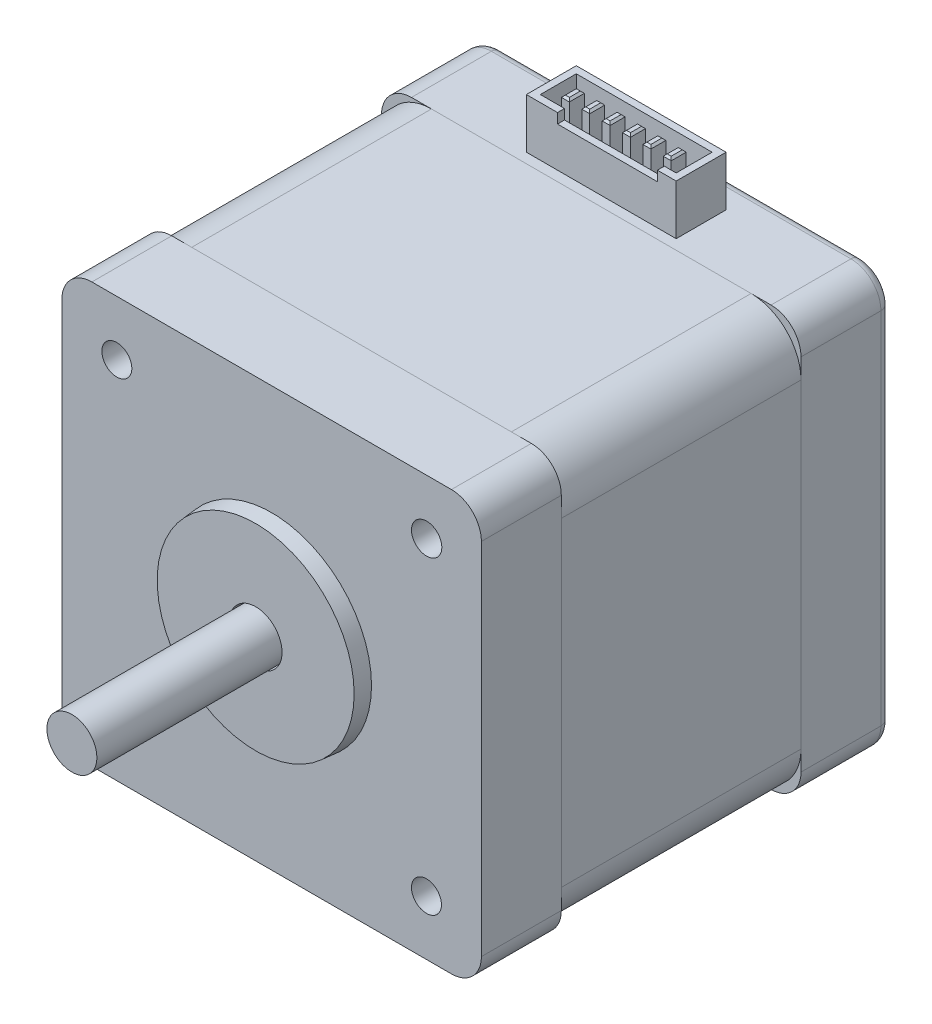
SolidWorks part; units mm, degrees
material "氧化铝"
ref_plane "前视基准面" through (0, 0, 0) normal (0, 0, 1) x (1, 0, 0)
ref_plane "上视基准面" through (0, 0, 0) normal (0, 1, 0) x (1, 0, 0)
ref_plane "右视基准面" through (0, 0, 0) normal (1, 0, 0) x (0, 0, -1)
sketch "草图1" plane through (0, 0, 0) normal (0, 0, 1) x (1, 0, 0)
  line L0 (0, 21) -> (0, -21) construction
  line L1 (-18, 21) -> (18, 21)
  line L2 (-21, 18) -> (-21, -18)
  line L3 (-18, -21) -> (18, -21)
  line L4 (21, 18) -> (21, -18)
  line L5 (-21, 21) -> (21, -21) construction
  line L6 (-21, -21) -> (21, 21) construction
  line L7 (-15.5, 15.5) -> (15.5, 15.5) construction
  line L8 (-15.5, 15.5) -> (-15.5, -15.5) construction
  line L9 (-15.5, -15.5) -> (15.5, -15.5) construction
  line L10 (15.5, 15.5) -> (15.5, -15.5) construction
  line L11 (-15.5, 15.5) -> (15.5, -15.5) construction
  line L12 (-15.5, -15.5) -> (15.5, 15.5) construction
  line L13 (-21, 0) -> (21, 0) construction
  circle A0 centre (-15.5, 15.5) radius 1.5
  circle A1 centre (15.5, 15.5) radius 1.5
  circle A2 centre (15.5, -15.5) radius 1.5
  circle A3 centre (-15.5, -15.5) radius 1.5
  arc A4 (-18, -21) -> (-21, -18) centre (-18, -18) cw
  arc A5 (18, -21) -> (21, -18) centre (18, -18) ccw
  arc A6 (21, 18) -> (18, 21) centre (18, 18) ccw
  arc A7 (-21, 18) -> (-18, 21) centre (-18, 18) cw
  point P0 (0, 0)
  point P6 (0, 0)
  dimension "D4" = 3
  dimension "D5" = 3
  dimension "D1" = 42
  dimension "D2" = 42
  dimension "D3" = 31
extrude "凸台-拉伸1" add sketch "草图1" along normal blind 8
sketch "草图4" plane through (0, 0, 8) normal (0, 0, 1) x (1, 0, 0)
  circle A0 centre (0, 0) radius 2.5
  dimension "D1" = 5
extrude "凸台-拉伸2" add sketch "草图4" along normal blind 20
sketch "草图9" plane through (0, 0, 0) normal (0, 0, -1) x (-1, 0, 0)
  line L1 (-21, 21) -> (21, 21)
  line L2 (-21, 21) -> (-21, -21)
  line L3 (-21, -21) -> (21, -21)
  line L4 (21, 21) -> (21, -21)
  line L5 (-21, 21) -> (21, -21) construction
  line L6 (-21, -21) -> (21, 21) construction
  point P0 (0, 0)
  dimension "D1" = 42
  dimension "D2" = 42
extrude "凸台-拉伸7" add sketch "草图9" along normal blind 24 separate body
sketch "草图10" plane through (0, 0, -24) normal (0, 0, -1) x (-1, 0, 0)
  line L1 (-21, 21) -> (21, 21)
  line L2 (-21, 21) -> (-21, -21)
  line L3 (-21, -21) -> (21, -21)
  line L4 (21, 21) -> (21, -21)
extrude "凸台-拉伸8" add sketch "草图10" along normal blind 9 separate body
fillet "圆角1" radius 3 4 edges at (21, -21, -28.5) (-21, -21, -28.5) (-21, 21, -28.5) (21, 21, -28.5)
fillet "圆角2" radius 5 4 edges at (-21, -21, -12) (-21, 21, -12) (21, 21, -12) (21, -21, -12)
sketch "草图12" plane through (0, 0, 8) normal (0, 0, 1) x (1, 0, 0)
  circle A0 centre (-15.5, 15.5) radius 1.5
  circle A1 centre (15.5185, 15.5) radius 1.5185
  circle A2 centre (-15.5, -15.5) radius 1.5
  circle A3 centre (15.5, -15.5) radius 1.5
extrude "切除-拉伸1" cut sketch "草图12" against normal through all
sketch "草图13" plane through (0, 0, -33) normal (0, 0, -1) x (-1, 0, 0)
  circle A0 centre (0, 0) radius 2.5
extrude "凸台-拉伸9" [suppressed] add sketch "草图13" along normal blind 12
sketch "草图14" plane through (0, 21, 0) normal (0, 1, 0) x (1, 0, 0)
  line L0 (-18, 33) -> (18, 33) construction
  line L1 (-7.5, 30) -> (7.5, 30)
  line L2 (-7.5, 30) -> (-7.5, 25)
  line L3 (-7.5, 25) -> (7.5, 25)
  line L4 (7.5, 30) -> (7.5, 25)
  line L5 (-6.8, 29.3) -> (6.8, 29.3)
  line L6 (6.8, 29.3) -> (6.8, 25.7)
  line L7 (-6.8, 25.7) -> (6.8, 25.7)
  line L8 (-6.8, 29.3) -> (-6.8, 25.7)
  line L9 (-3.66, 28.2073) -> (-2.86, 28.2073)
  line L10 (-5.7, 28.2073) -> (-4.9, 28.2073)
  line L11 (-5.7, 28.2073) -> (-5.7, 26.7073)
  line L12 (-5.7, 26.7073) -> (-4.9, 26.7073)
  line L13 (-4.9, 28.2073) -> (-4.9, 26.7073)
  line L14 (-5.7, 28.2073) -> (-4.9, 26.7073) construction
  line L15 (-5.7, 26.7073) -> (-4.9, 28.2073) construction
  line L16 (-3.66, 28.2073) -> (-3.66, 26.7073)
  line L17 (-3.66, 26.7073) -> (-2.86, 26.7073)
  line L18 (-2.86, 28.2073) -> (-2.86, 26.7073)
  line L19 (-3.66, 28.2073) -> (-2.86, 26.7073) construction
  line L20 (-3.66, 26.7073) -> (-2.86, 28.2073) construction
  line L21 (-1.62, 28.2073) -> (-0.82, 28.2073)
  line L22 (-1.62, 28.2073) -> (-1.62, 26.7073)
  line L23 (-1.62, 26.7073) -> (-0.82, 26.7073)
  line L24 (-0.82, 28.2073) -> (-0.82, 26.7073)
  line L25 (-1.62, 28.2073) -> (-0.82, 26.7073) construction
  line L26 (-1.62, 26.7073) -> (-0.82, 28.2073) construction
  line L27 (0.42, 28.2073) -> (1.22, 28.2073)
  line L28 (0.42, 28.2073) -> (0.42, 26.7073)
  line L29 (0.42, 26.7073) -> (1.22, 26.7073)
  line L30 (1.22, 28.2073) -> (1.22, 26.7073)
  line L31 (0.42, 28.2073) -> (1.22, 26.7073) construction
  line L32 (0.42, 26.7073) -> (1.22, 28.2073) construction
  line L33 (2.46, 28.2073) -> (3.26, 28.2073)
  line L34 (2.46, 28.2073) -> (2.46, 26.7073)
  line L35 (2.46, 26.7073) -> (3.26, 26.7073)
  line L36 (3.26, 28.2073) -> (3.26, 26.7073)
  line L37 (2.46, 28.2073) -> (3.26, 26.7073) construction
  line L38 (2.46, 26.7073) -> (3.26, 28.2073) construction
  line L39 (4.5, 28.2073) -> (5.3, 28.2073)
  line L40 (4.5, 28.2073) -> (4.5, 26.7073)
  line L41 (4.5, 26.7073) -> (5.3, 26.7073)
  line L42 (5.3, 28.2073) -> (5.3, 26.7073)
  line L43 (4.5, 28.2073) -> (5.3, 26.7073) construction
  line L44 (4.5, 26.7073) -> (5.3, 28.2073) construction
  line L45 (0, 33) -> (0, 30) construction
  point P11 (-5.3, 27.4573)
  point P18 (-3.26, 27.4573)
  point P23 (-1.22, 27.4573)
  point P28 (0.82, 27.4573)
  point P33 (2.86, 27.4573)
  point P38 (4.9, 27.4573)
  dimension "D1" = 15
  dimension "D2" = 5
  dimension "D3" = 3
  dimension "D4" = 0.7
  dimension "D5" = 1.5
  dimension "D6" = 0.8
  dimension "D8" = 1.5
  dimension "D9" = 1.5
  dimension "D7" = 6
extrude "凸台-拉伸10" add sketch "草图14" along normal blind 5 contours L4 L1 L2 L3 L8 L5 L6 L7 | L13 L10 L11 L12 | L24 L21 L22 L23 | L42 L39 L40 L41 | L36 L33 L34 L35 | L9 L18 L17 L16 | L27 L30 L29 L28 region at (0, 21, -29.8419) region at (-5.3, 21, -27.4573) region at (-1.22, 21, -27.4573) region at (2.86, 21, -27.4573) region at (4.9, 21, -27.4573)
chamfer "倒角1" distance 0.2 angle 45 24 edges at (4.9, 26, -26.7073) (4.5, 26, -27.4573) (4.9, 26, -28.2073) (5.3, 26, -27.4573) (2.86, 26, -26.7073) (2.46, 26, -27.4573) (2.86, 26, -28.2073) (3.26, 26, -27.4573) (0.82, 26, -28.2073) (1.22, 26, -27.4573) (0.82, 26, -26.7073) (0.42, 26, -27.4573) (-1.22, 26, -26.7073) (-1.62, 26, -27.4573) (-1.22, 26, -28.2073) (-0.82, 26, -27.4573) (-3.26, 26, -28.2073) (-2.86, 26, -27.4573) (-3.26, 26, -26.7073) (-3.66, 26, -27.4573) (-5.3, 26, -26.7073) (-5.7, 26, -27.4573) (-5.3, 26, -28.2073) (-4.9, 26, -27.4573)
sketch "草图15" plane through (0, 0, -25) normal (0, 0, 1) x (1, 0, 0)
  line L0 (0.62, 26) -> (0.62, 22.2151) construction
  line L1 (-4.38, 26) -> (-4.38, 25)
  line L2 (-7.5, 26) -> (7.5, 26) construction
  line L3 (-4.38, 25) -> (5.62, 25)
  line L4 (5.62, 26) -> (5.62, 25)
  line L5 (-4.38, 26) -> (5.62, 26)
  point P9 (0.62, 25)
  dimension "D1" = 5
  dimension "D2" = 1
extrude "切除-拉伸2" cut sketch "草图15" against normal up to next (0.7 mm away)
fillet "圆角3" radius 1 8 edges at (20.1213, 20.1213, -33) (-20.1213, 20.1213, -33) (-21, 0, -33) (-20.1213, -20.1213, -33) (0, -21, -33) (20.1213, -20.1213, -33) (21, 0, -33) (0, 21, -33)
sketch "草图16" plane through (0, 0, 8) normal (0, 0, 1) x (1, 0, 0)
  circle A0 centre (0, 0) radius 10
  circle A1 centre (0, 0) radius 2.5 construction
  circle A2 centre (0, 0) radius 2.5
  dimension "D1" = 20
extrude "凸台-拉伸11" add sketch "草图16" along normal blind 1.6 draft 5
sketch "草图17" plane through (0, 0, -33) normal (0, 0, -1) x (-1, 0, 0)
  circle A0 centre (0, 0) radius 2.5
  dimension "D1" = 5
extrude "凸台-拉伸12" [suppressed] add sketch "草图17" along normal blind 15
sketch "草图18" plane through (0, 0, -33) normal (0, 0, -1) x (-1, 0, 0)
  circle A0 centre (0, 0) radius 5
  dimension "D1" = 10
extrude "切除-拉伸3" cut sketch "草图18" against normal blind 3
sketch "草图19" plane through (0, 0, -30) normal (0, 0, -1) x (-1, 0, 0)
  circle A0 centre (0, 0) radius 2.5
  dimension "D1" = 5
extrude "凸台-拉伸13" add sketch "草图19" along normal blind 2
ref_axis "基准轴1" through (0, 0, 67.221) along (0, 0, -1)
